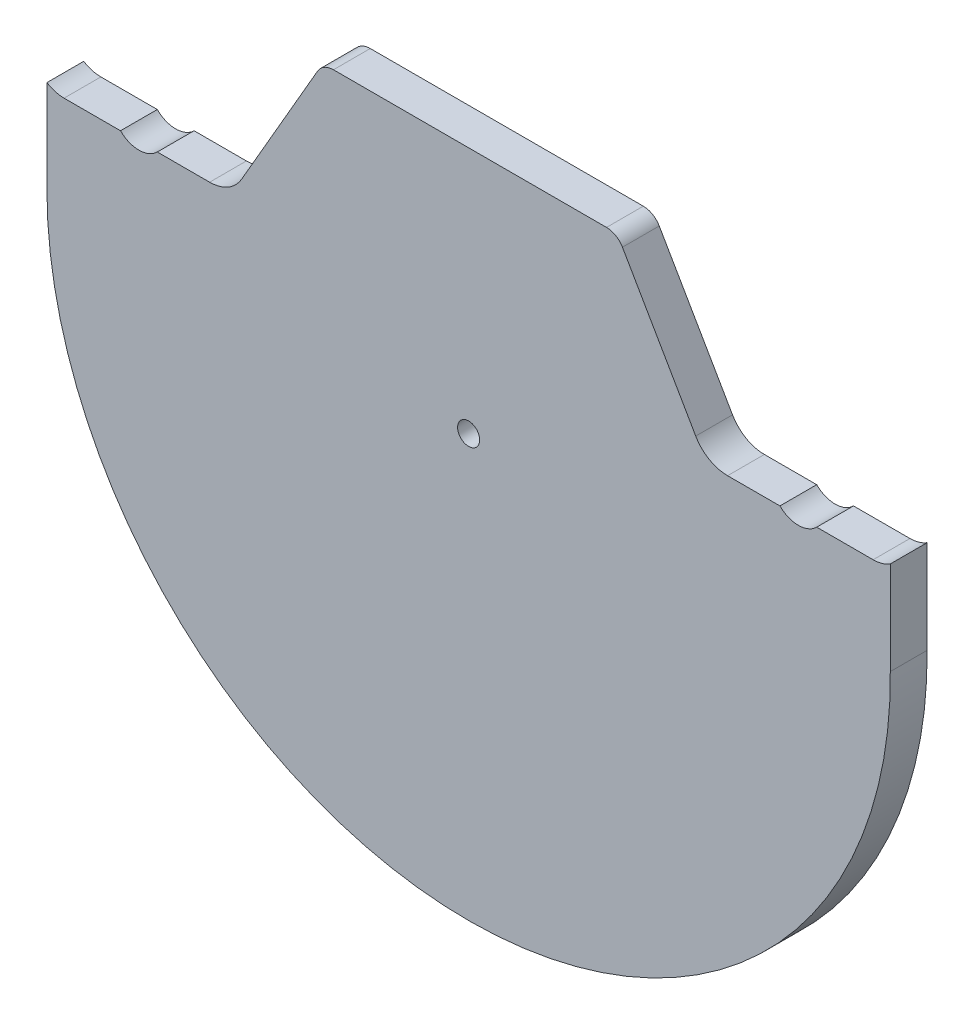
SolidWorks part; units mm, degrees
material "Balsa"
ref_plane "Ebene vorne" through (0, 0, 0) normal (0, 0, 1) x (1, 0, 0)
ref_plane "Ebene oben" through (0, 0, 0) normal (0, 1, 0) x (1, 0, 0)
ref_plane "Ebene rechts" through (0, 0, 0) normal (1, 0, 0) x (0, 0, -1)
sketch "Skizze2" plane through (0, 0, 0) normal (0, 0, 1) x (1, 0, 0)
  line L0 (1.4434, 0) -> (38.5566, 0)
  line L1 (40.7217, -1.25) -> (50.6801, -18.4986)
  line L2 (40, 14.0859) -> (40, -17.6492) construction
  line L3 (55.0103, -20.9986) -> (62.1235, -20.9986)
  line L4 (67.1235, -20.9986) -> (74.7933, -20.9986)
  line L5 (77.1235, -20.3287) -> (77.1235, -32.9986)
  line L6 (-27.5, -21.6506) -> (-35.17, -21.6506)
  line L7 (-37.501, -20.9806) -> (-37.5, -33.6506)
  line L8 (0, 11.7679) -> (0, -17.6492) construction
  line L9 (-0.7217, -1.25) -> (-11.0566, -19.1506)
  line L10 (-15.3868, -21.6506) -> (-22.5, -21.6506)
  line L17 (19.8136, 38.5591) -> (19.8136, -113.1503) construction
  arc A0 (40.7217, -1.25) -> (38.5566, 0) centre (38.5566, -2.5) ccw
  arc A1 (55.0103, -20.9986) -> (50.6801, -18.4986) centre (55.0103, -15.9986) cw
  arc A2 (-0.7217, -1.25) -> (1.4434, 0) centre (1.4434, -2.5) cw
  arc A3 (-15.3868, -21.6506) -> (-11.0566, -19.1506) centre (-15.3868, -16.6506) ccw
  arc A4 (-37.5, -33.6506) -> (77.1235, -32.9986) centre (19.8136, -33.6506) ccw
  arc A5 (-35.17, -21.6506) -> (-37.501, -20.9806) centre (-35.17, -17.2606) cw
  arc A6 (74.7933, -20.9986) -> (77.1235, -20.3287) centre (74.7933, -16.6107) ccw
  circle A7 centre (19.8136, -33.6506) radius 1.5
  arc A8 (67.1235, -20.9986) -> (62.1235, -20.9986) centre (64.6235, -18.4986) cw
  arc A9 (-27.5, -21.6506) -> (-22.5, -21.6506) centre (-25, -19.1506) ccw
  point P8 (40, 0)
  point P16 (52.1235, -20.9986)
  point P22 (0, 0)
  point P30 (-12.5, -21.6506)
  point P34 (-25, -22.6862)
  point P35 (0, 0)
  point P37 (-37.68, -21.6506)
  point P43 (-36.8636, -21.6506)
  dimension "D2" = 2.5
  dimension "D4" = 30
  dimension "D9" = 5
  dimension "D12" = 2.5
  dimension "D17" = 5
  dimension "D20" = 57.3136
  dimension "D21" = 12.67
  dimension "D22" = 4.3879
  dimension "D23" = 3
  dimension "D6" = 3.5355
  dimension "D14" = 3.5355
  dimension "D16" = 4.39
  dimension "D25" = 2.5
  dimension "D1" = 40
  dimension "D3" = 25
  dimension "D5" = 10
  dimension "D7" = 2.5
  dimension "D8" = 7.6698
  dimension "D10" = 25
  dimension "D11" = 30
  dimension "D13" = 10
  dimension "D15" = 7.67
  dimension "D18" = 12.6699
  dimension "D19" = 12
  dimension "D24" = 12
  dimension "D26" = 12.5
extrude "Aufsatz-Linear austragen1" add sketch "Skizze2" along normal blind 5
